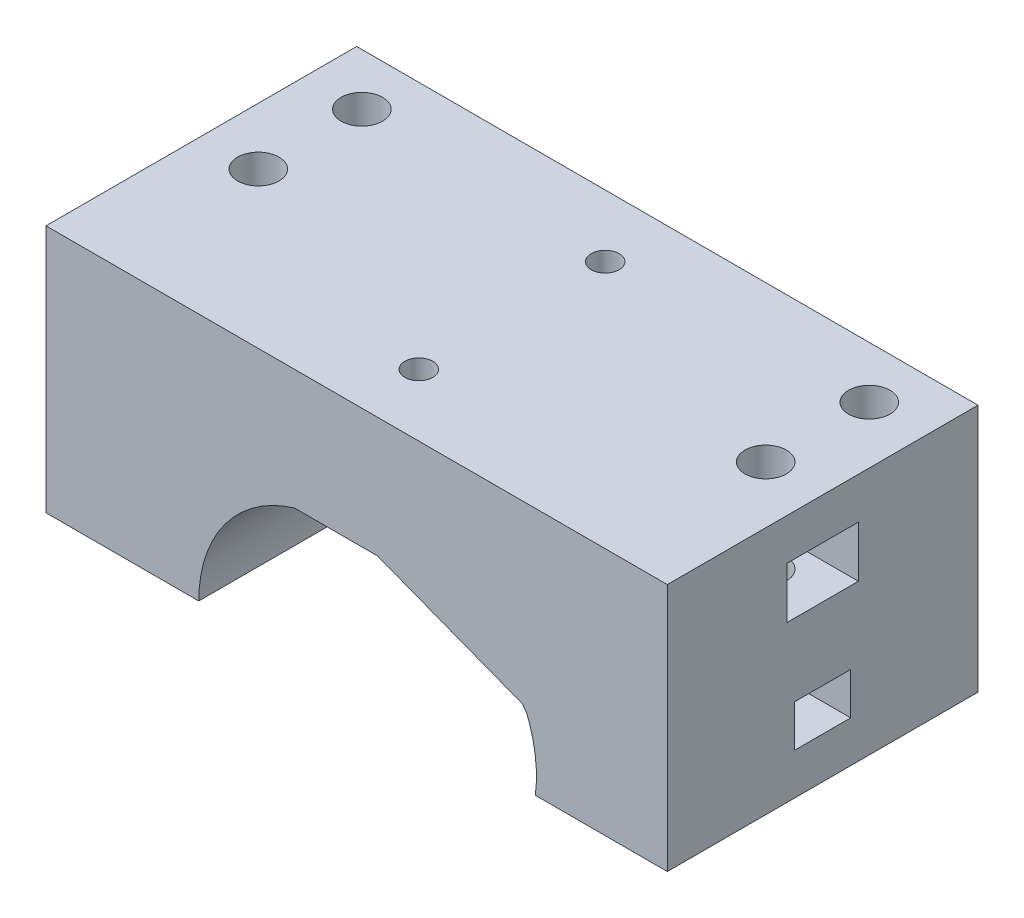
SolidWorks part; units mm, degrees
material "6061 合金"
ref_plane "前视基准面" through (0, 0, 0) normal (0, 0, 1) x (1, 0, 0)
ref_plane "上视基准面" through (0, 0, 0) normal (0, 1, 0) x (1, 0, 0)
ref_plane "右视基准面" through (0, 0, 0) normal (1, 0, 0) x (0, 0, -1)
sketch "草图1" plane through (0, 0, 0) normal (0, 0, 1) x (1, 0, 0)
  line L1 (-30, 17) -> (30, 17)
  line L2 (-30, 17) -> (-30, -17)
  line L3 (-30, -17) -> (30, -17)
  line L4 (30, 17) -> (30, -17)
  line L5 (-30, 17) -> (30, -17) construction
  line L6 (-30, -17) -> (30, 17) construction
  point P0 (0, 0)
  dimension "D1" = 34
  dimension "D2" = 60
extrude "凸台-拉伸1" add sketch "草图1" along normal blind 30
sketch "草图2" plane through (0, 0, 30) normal (0, 0, 1) x (1, 0, 0)
  line L0 (0, 0) -> (7.95, 0) construction
  line L1 (-11.5, 0) -> (-13.5, 0)
  line L2 (-13.5, 0) -> (-13.5, 15.766)
  line L4 (0, 0) -> (-35, 0)
  line L5 (-35, 0) -> (-35, 6.18)
  line L6 (-35, 6.18) -> (22.6518, 15.3111)
  line L7 (-13.5, 15.766) -> (-8.5, 15.766)
  line L8 (-8.5, 15.766) -> (-8.5, 10.3779)
  line L9 (0, 0) -> (11.5, 0)
  line L10 (11.5, 0) -> (11.5, 7.35)
  line L11 (0, 0) -> (0, -6.5) construction
  arc A0 (-8.5, 10.3779) -> (-11.5, 0) centre (7.95, 0) ccw
  arc A1 (-2.4955, 11.3282) -> (11.5, 7.35) centre (0, -6.5) cw
  dimension "D2" = 19.45
  dimension "D1" = 7.95
  dimension "D3" = 3
  dimension "D4" = 5
  dimension "D5" = 35
  dimension "D6" = 9
  dimension "D7" = 6.18
  dimension "D8" = 11.5
  dimension "D9" = 7.35
  dimension "D10" = 6.5
extrude "切除-拉伸1" [suppressed] cut sketch "草图2" against normal through all contours A1 L6 A0 L4 L9 L10
mirror "镜向1" [suppressed] about plane through (0, 0, 0) normal (0, 1, 0)
fillet "圆角1" [suppressed] radius 2
fillet "圆角2" [suppressed] radius 1
sketch "草图3" [suppressed] plane through (0, 0, 30) normal (0, 0, 1) x (1, 0, 0)
  line L0 (0, 0) -> (10.98, 0) construction
  line L1 (11.5, -6.8723) -> (11.5, 6.8723) construction
  line L2 (11.5, 8.0833) -> (11.5, -8.0833)
  arc A0 (11.5, 8.0833) -> (11.5, -8.0833) centre (10.98, 0) cw
  dimension "D2" = 8.1
  dimension "D1" = 10.98
extrude "切除-拉伸2" [suppressed] cut sketch "草图3" against normal through all
sketch "草图4" plane through (-30, 0, 0) normal (-1, 0, 0) x (0, 0, 1)
  line L0 (-9.8218, 0) -> (27.8243, 0) construction
  line L1 (0, 17) -> (30, 17)
  line L2 (0, 17) -> (0, 28)
  line L3 (0, 28) -> (30, 28)
  line L4 (30, 17) -> (30, 28)
  line L5 (30, 17) -> (30, -17) construction
  line L6 (15, 28) -> (15, -28) construction
  line L7 (0, -17) -> (30, -17)
  line L8 (0, -17) -> (0, -28)
  line L9 (0, -28) -> (30, -28)
  line L10 (30, -17) -> (30, -28)
  circle A0 centre (15, 24) radius 1.6
  circle A1 centre (15, -24) radius 1.6
  dimension "D2" = 3.2
  dimension "D3" = 48
  dimension "D1" = 56
extrude "凸台-拉伸2" [suppressed] add sketch "草图4" along normal blind 6 from surface
sketch "草图5" [suppressed] plane through (0, -17, 0) normal (0, -1, 0) x (1, 0, 0)
  line L1 (-20, 20) -> (20, 20)
  line L2 (-20, 20) -> (-20, 0)
  line L3 (-20, 0) -> (20, 0)
  line L4 (20, 20) -> (20, 0)
fillet "圆角3" [suppressed] radius 10
sketch "草图8" plane through (0, 0, 30) normal (0, 0, 1) x (1, 0, 0)
sketch "草图9" [suppressed] plane through (0, 0, 30) normal (0, 0, 1) x (1, 0, 0)
  line L1 (-37, 17) -> (-12, 17)
  line L2 (-37, 17) -> (-37, 29)
  line L3 (-37, 29) -> (-12, 29)
  line L4 (-12, 17) -> (-12, 29)
  line L5 (30, 0) -> (-45.0994, 0) construction
  line L7 (30, -28) -> (30, 28) construction
  line L8 (-12, -17) -> (-12, -29)
  line L9 (-37, -29) -> (-12, -29)
  line L10 (-37, -17) -> (-37, -29)
  line L11 (-37, -17) -> (-12, -17)
  line L12 (-31, 24.5) -> (-21, 24.5) construction
  line L13 (24, 17) -> (-30, 17) construction
  line L14 (24, 17) -> (24, 28) construction
  circle A0 centre (-31, 24.5) radius 2
  circle A1 centre (-21, 24.5) radius 2
  circle A2 centre (-21, -24.5) radius 2
  circle A3 centre (-31, -24.5) radius 2
  dimension "D3" = 49
  dimension "D4" = 4
  dimension "D5" = 4
  dimension "D6" = 10
  dimension "D7" = 36
  dimension "D8" = 45
  dimension "D1" = 12
  dimension "D2" = 25
extrude "凸台-拉伸5" [suppressed] add sketch "草图9" against normal blind 65
fillet "圆角4" [suppressed] radius 10
sketch "草图10" [suppressed] plane through (-37, 0, 0) normal (-1, 0, 0) x (0, 0, 1)
  line L0 (0, 0) -> (61.2796, 0) construction
  line L1 (30, -17) -> (30, -29) construction
  circle A0 centre (15, 24) radius 2.1
  circle A1 centre (15, -24) radius 2.1
  dimension "D1" = 4.2
  dimension "D2" = 48
  dimension "D3" = 15
extrude "切除-拉伸3" [suppressed] cut sketch "草图10" against normal blind 40
fillet "圆角5" [suppressed] radius 6
extrude "凸台-拉伸3" [suppressed] add sketch "草图5" along normal blind 60
sketch "草图6" [suppressed] plane through (0, 0, 20) normal (0, 0, 1) x (1, 0, 0)
  line L0 (-20, 17) -> (-20, -77) construction
  line L1 (20, -77) -> (-20, -77)
  line L2 (20, -77) -> (20, -27)
  line L3 (20, -27) -> (-20, -27)
  line L4 (-20, -77) -> (-20, -27)
  dimension "D1" = 50
extrude "凸台-拉伸4" [suppressed] add sketch "草图6" along normal blind 60
sketch "草图12" [suppressed] plane through (0, -29, 0) normal (0, -1, 0) x (1, 0, 0)
  line L0 (-37, -35) -> (-37, 30) construction
  line L1 (-34.4, -18.7) -> (-17.2, -18.7)
  line L2 (-34.4, -18.7) -> (-34.4, -23)
  line L3 (-34.4, -23) -> (-17.2, -23)
  line L4 (-17.2, -18.7) -> (-17.2, -23)
  line L5 (-37, -35) -> (-12, -35) construction
  dimension "D1" = 4.3
  dimension "D2" = 17.2
  dimension "D3" = 2.6
  dimension "D4" = 12
extrude "切除-拉伸4" [suppressed] cut sketch "草图12" against normal blind 8.8
mirror "镜向2" [suppressed] about plane through (0, 0, 0) normal (0, 1, 0)
sketch "草图13" [suppressed] plane through (0, 0, 30) normal (0, 0, 1) x (1, 0, 0)
  circle A0 centre (-21, 24.5) radius 2
  circle A1 centre (-31, 24.5) radius 2
  circle A2 centre (-31, -24.5) radius 2
  circle A3 centre (-21, -24.5) radius 2
extrude "凸台-拉伸6" [suppressed] add sketch "草图13" against normal blind 40
sketch "草图17" plane through (0, 0, 0) normal (0, 0, -1) x (-1, 0, 0)
  line L0 (-30, 17) -> (30, 17) construction
  line L1 (30, 17) -> (18, 17)
  line L2 (30, 17) -> (30, 40)
  line L3 (30, 40) -> (18, 40)
  line L4 (18, 17) -> (18, 40)
  line L5 (-18, 17) -> (-30, 17)
  line L6 (-18, 17) -> (-18, 40)
  line L7 (-18, 40) -> (-30, 40)
  line L8 (-30, 17) -> (-30, 40)
  line L9 (-30, -17) -> (-30, 17) construction
  dimension "D1" = 23
  dimension "D2" = 23
  dimension "D3" = 12
  dimension "D4" = 12
extrude "凸台-拉伸8" add sketch "草图17" against normal blind 80
sketch "草图18" plane through (0, 0, 80) normal (0, 0, 1) x (1, 0, 0)
  line L0 (0, 0) -> (0, 43.5188) construction
  line L1 (18, 40) -> (30, 40) construction
  circle A0 centre (24.5, 34) radius 2
  circle A1 centre (24.5, 24) radius 2
  circle A2 centre (-24.5, 24) radius 2
  circle A3 centre (-24.5, 34) radius 2
  dimension "D1" = 49
  dimension "D2" = 49
  dimension "D3" = 4
  dimension "D4" = 4
  dimension "D5" = 10
  dimension "D6" = 6
extrude "切除-拉伸7" cut sketch "草图18" against normal blind 10
sketch "草图19" plane through (0, 0, 30) normal (0, 0, 1) x (1, 0, 0)
  line L0 (2, 12.4) -> (-6, 12.4)
  line L1 (2, 12.4) -> (16.0037, 7.0245)
  line L2 (2, 0) -> (2, 12.4) construction
  line L3 (2, 0) -> (-30, 0) construction
  line L4 (-30, 17) -> (-30, -17) construction
  line L5 (2, -12.4) -> (-6, -12.4)
  line L6 (2, -12.4) -> (16.0037, -7.0245)
  line L7 (18, 17) -> (-18, 17) construction
  line L8 (6.25, 0) -> (0, 0) construction
  line L9 (-30, -17) -> (30, -17) construction
  line L10 (0, 0) -> (-3.1579, 0) construction
  line L11 (-2.4742, 0) -> (1.2749, 0) construction
  arc A3 (16.0037, 7.0245) -> (16.0037, -7.0245) centre (-3.1579, 0) cw
  arc A4 (-6, 12.4) -> (-6, -12.4) centre (-2.3127, 0) ccw
  point P10 (1.2749, 0)
  point P21 (17.2507, 0)
  point P36 (-15.2493, 0)
  dimension "D6" = 2
  dimension "D7" = 15
  dimension "D3" = 32.5
  dimension "D9" = 15
  dimension "D1" = 12.4
  dimension "D2" = 8
  dimension "D4" = 21
  dimension "D8" = 21
extrude "切除-拉伸8" cut sketch "草图19" against normal blind 66
sketch "草图20" plane through (30, 0, 0) normal (1, 0, 0) x (0, 0, -1)
  line L0 (-80, 40) -> (-80, 17) construction
  line L1 (-70, 37.4) -> (-65.5, 37.4)
  line L2 (-70, 37.4) -> (-70, 20.2)
  line L3 (-70, 20.2) -> (-65.5, 20.2)
  line L4 (-65.5, 37.4) -> (-65.5, 20.2)
  line L5 (-80, 40) -> (0, 40) construction
  dimension "D1" = 10
  dimension "D2" = 4.5
  dimension "D3" = 2.6
  dimension "D4" = 17.2
extrude "切除-拉伸9" cut sketch "草图20" against normal blind 8.8
sketch "草图14" plane through (0, -17, 0) normal (0, -1, 0) x (1, 0, 0)
  line L0 (0, 0) -> (0, 30) construction
  line L1 (-28, 0) -> (28, 0)
  line L2 (-28, 0) -> (-28, 30)
  line L3 (-28, 30) -> (28, 30)
  line L4 (28, 0) -> (28, 30)
  line L5 (-28, 0) -> (28, 30) construction
  line L6 (-28, 30) -> (28, 0) construction
  line L7 (0, 15) -> (24.5, 15) construction
  line L8 (-30, 30) -> (30, 30) construction
  line L9 (-30, 0) -> (30, 0) construction
  line L10 (30, 30) -> (18, 30) construction
  circle A0 centre (24.5, 15) radius 1.6
  circle A1 centre (-24.5, 15) radius 1.6
  point P0 (0, 15)
  dimension "D2" = 3.2
  dimension "D3" = 49
  dimension "D1" = 56
extrude "切除-拉伸6" cut sketch "草图14" against normal through all contours A0 | A1 region at (24.5, -17, 15) region at (-24.5, -17, 15)
mirror "镜向3" about plane through (0, 0, 0) normal (1, 0, 0) of "切除-拉伸9"
sketch "草图21" plane through (0, -17, 0) normal (0, -1, 0) x (1, 0, 0)
  line L1 (-30, 30) -> (30, 30)
  line L2 (-30, 30) -> (-30, 0)
  line L3 (-30, 0) -> (30, 0)
  line L4 (30, 30) -> (30, 0)
  circle A0 centre (24.5, 15) radius 1.6
  circle A1 centre (-24.5, 15) radius 1.6
extrude "凸台-拉伸9" add sketch "草图21" along normal blind 7
sketch "草图22" plane through (0, 17, 0) normal (0, 1, 0) x (1, 0, 0)
  line L1 (-18, 0) -> (18, 0)
  line L2 (-18, 0) -> (-18, -30)
  line L3 (-18, -30) -> (18, -30)
  line L4 (18, 0) -> (18, -30)
extrude "凸台-拉伸10" add sketch "草图22" along normal blind 7
sketch "草图25" plane through (-30, 0, 0) normal (-1, 0, 0) x (0, 0, 1)
  line L0 (0, 40) -> (0, -24) construction
  line L1 (0, 24) -> (30, 24)
  line L2 (0, 24) -> (0, -24)
  line L3 (0, -24) -> (30, -24)
  line L4 (30, 24) -> (30, -24)
  line L5 (0, 24) -> (30, -24) construction
  line L6 (0, -24) -> (30, 24) construction
  line L7 (8, 16) -> (8, -16) construction
  line L8 (15, 0) -> (15, -12.6905) construction
  circle A0 centre (8, -16) radius 1.5
  circle A1 centre (8, 16) radius 1.5
  circle A2 centre (22, -16) radius 1.5
  circle A3 centre (22, 16) radius 1.5
  point P0 (15, 0)
  point P11 (15, 0)
  dimension "D2" = 3
  dimension "D3" = 3
  dimension "D1" = 32
  dimension "D4" = 7
extrude "切除-拉伸12" [suppressed] cut sketch "草图25" against normal blind 108 contours A1 | A0 | A3 | A2
sketch "草图23" plane through (0, 0, 0) normal (1, 0, 0) x (0, 0, -1)
  line L1 (34.3948, -41.3985) -> (-105.7517, -41.3985)
  line L2 (34.3948, -41.3985) -> (34.3948, 61.9184)
  line L3 (34.3948, 61.9184) -> (-105.7517, 61.9184)
  line L4 (-105.7517, -41.3985) -> (-105.7517, 61.9184)
extrude "切除-拉伸10" [suppressed] cut sketch "草图23" against normal blind 108
sketch "草图24" plane through (0, 0, 0) normal (1, 0, 0) x (0, 0, -1)
  line L5 (-94.0825, 62.2673) -> (30.5955, 62.2673)
  line L6 (-94.0825, 62.2673) -> (-94.0825, -43.8021)
  line L7 (-94.0825, -43.8021) -> (30.5955, -43.8021)
  line L8 (30.5955, 62.2673) -> (30.5955, -43.8021)
extrude "切除-拉伸11" [suppressed] cut sketch "草图24" along normal blind 108
sketch "草图27" plane through (0, 17, 0) normal (0, -1, 0) x (1, 0, 0)
  line L1 (18, 30) -> (30, 30)
  line L2 (18, 30) -> (18, 80)
  line L3 (18, 80) -> (30, 80)
  line L4 (30, 30) -> (30, 80)
extrude "切除-拉伸13" cut sketch "草图27" against normal through all
ref_plane "基准面1" through (18, 40, 30) normal (1, 0, 0) x (0, 0, -1)
sketch "草图29" plane through (0, 0, 30) normal (0, 0, 1) x (1, 0, 0)
  line L1 (18, 24) -> (30, 24)
  line L2 (18, 24) -> (18, 40)
  line L3 (18, 40) -> (30, 40)
  line L4 (30, 24) -> (30, 40)
extrude "切除-拉伸14" cut sketch "草图29" against normal through all
sketch "草图30" [suppressed] plane through (0, 17, 0) normal (0, -1, 0) x (1, 0, 0)
  line L1 (-30, 80) -> (-18, 80)
  line L2 (-30, 80) -> (-30, 30)
  line L3 (-30, 30) -> (-18, 30)
  line L4 (-18, 80) -> (-18, 30)
extrude "切除-拉伸15" [suppressed] cut sketch "草图30" against normal through all
sketch "草图31" [suppressed] plane through (0, 0, 30) normal (0, 0, 1) x (1, 0, 0)
  line L1 (-18, 24) -> (-30, 24)
  line L2 (-18, 24) -> (-18, 40)
  line L3 (-18, 40) -> (-30, 40)
  line L4 (-30, 24) -> (-30, 40)
extrude "切除-拉伸16" [suppressed] cut sketch "草图31" against normal blind 87
sketch "草图32" [suppressed] plane through (0, 0, 30) normal (0, 0, 1) x (1, 0, 0)
  line L0 (-10, 24) -> (-13.4641, 22)
  line L2 (-30, 24) -> (0, 24) construction
  line L3 (-13.4641, 22) -> (0, 22)
  line L4 (0, 12.25) -> (0, 24) construction
  line L5 (-10, 24) -> (0, 24)
  line L6 (0, 24) -> (0, 22)
  dimension "D1" = 3
  dimension "D2" = 10
  dimension "D3" = 40
extrude "切除-拉伸17" [suppressed] cut sketch "草图32" against normal through all
sketch "草图33" [suppressed] plane through (0, 0, 30) normal (0, 0, 1) x (1, 0, 0)
  line L0 (13.5753, 21) -> (10, 24)
  line L1 (10, 24) -> (0, 24)
  line L2 (13.5753, 21) -> (0, 21)
  line L3 (0, 21) -> (0, 24)
  line L4 (0, 24) -> (30, 24) construction
  dimension "D1" = 40
  dimension "D2" = 10
  dimension "D3" = 3
extrude "切除-拉伸18" [suppressed] cut sketch "草图33" against normal through all
sketch "草图34" plane through (30, 0, 0) normal (1, 0, 0) x (0, 0, -1)
  line L0 (0, 0) -> (-30, 0) construction
  line L1 (-30, -24) -> (-30, 24) construction
  line L2 (0, -24) -> (0, 24) construction
  line L3 (-30, -11) -> (0, -11)
  line L4 (-30, -11) -> (-30, 11)
  line L5 (-30, 11) -> (0, 11)
  line L6 (0, -11) -> (0, 11)
  line L7 (-30, -11) -> (0, 11) construction
  line L8 (-30, 11) -> (0, -11) construction
  point P5 (-15, 0)
  dimension "D1" = 22
extrude "切除-拉伸19" [suppressed] cut sketch "草图34" against normal blind 8
sketch "草图35" [suppressed] plane through (-30, 0, 0) normal (-1, 0, 0) x (0, 0, 1)
  line L0 (0, 0) -> (30, 0) construction
  line L1 (30, 24) -> (30, -24) construction
  line L3 (0, -11) -> (30, -11)
  line L4 (0, -11) -> (0, 11)
  line L5 (0, 11) -> (30, 11)
  line L6 (30, -11) -> (30, 11)
  line L7 (0, -11) -> (30, 11) construction
  line L8 (0, 11) -> (30, -11) construction
  point P5 (15, 0)
  dimension "D1" = 22
extrude "切除-拉伸20" [suppressed] cut sketch "草图35" against normal blind 8
sketch "草图36" plane through (0, 0, 80) normal (0, 0, 1) x (1, 0, 0)
  line L1 (-30, 40) -> (-18, 40)
  line L2 (-30, 40) -> (-30, 17)
  line L3 (-30, 17) -> (-18, 17)
  line L4 (-18, 40) -> (-18, 17)
extrude "切除-拉伸21" cut sketch "草图36" against normal up to surface (50 mm away) up to face at (-6, 5.6667, 30)
sketch "草图37" plane through (0, 0, 30) normal (0, 0, 1) x (1, 0, 0)
  line L1 (-30, 40) -> (-18, 40)
  line L2 (-30, 40) -> (-30, 24)
  line L3 (-30, 24) -> (-18, 24)
  line L4 (-18, 40) -> (-18, 24)
extrude "切除-拉伸22" cut sketch "草图37" against normal through all
mirror "镜向4" [suppressed] about plane through (0, 0, 0) normal (1, 0, 0)
sketch "草图38" plane through (0, 0, 0) normal (0, 1, 0) x (1, 0, 0)
  line L1 (-30, 0) -> (30, 0)
  line L2 (-30, 0) -> (-30, -30)
  line L3 (-30, -30) -> (30, -30)
  line L4 (30, 0) -> (30, -30)
extrude "切除-拉伸23" cut sketch "草图38" against normal blind 34
sketch "草图40" plane through (0, 0, 30) normal (0, 0, 1) x (1, 0, 0)
  line L0 (0, 0) -> (0, 51.3105) construction
  line L1 (-10, 24) -> (-13.5753, 27)
  line L2 (-30, 24) -> (30, 24) construction
  line L3 (-13.5753, 27) -> (13.5753, 27)
  line L4 (10, 24) -> (13.5753, 27)
  line L5 (-10, 24) -> (10, 24)
  line L6 (-30, 24) -> (36.4336, 24) construction
  line L7 (-10, 24) -> (-13.5753, 21)
  line L8 (-13.5753, 21) -> (13.5753, 21)
  line L9 (10, 24) -> (13.5753, 21)
  point P10 (0, 27)
  line M8 (30, 24) -> (-30, 24)
  dimension "D1" = 3
  dimension "D2" = 40
  dimension "D3" = 10
extrude "切除-拉伸24" [suppressed] cut sketch "草图40" against normal up to surface (30 mm away) contours L9 L7 L8 M8
sketch "草图41" plane through (30, 0, 0) normal (1, 0, 0) x (0, 0, -1)
  line L0 (-15, 0) -> (-15, 24) construction
  line L1 (-30, 0) -> (0, 0) construction
  line L2 (0, 24) -> (-30, 24) construction
  line L6 (-18.45, 20) -> (-11.55, 20)
  line L7 (-18.45, 20) -> (-18.45, 15.05)
  line L8 (-18.45, 15.05) -> (-11.55, 15.05)
  line L9 (-11.55, 20) -> (-11.55, 15.05)
  line L10 (-18.45, 20) -> (-11.55, 15.05) construction
  line L11 (-18.45, 15.05) -> (-11.55, 20) construction
  line L12 (-17.705, 8.05) -> (-12.295, 8.05)
  line L13 (-17.705, 8.05) -> (-17.705, 4)
  line L14 (-17.705, 4) -> (-12.295, 4)
  line L15 (-12.295, 8.05) -> (-12.295, 4)
  line L16 (-17.705, 8.05) -> (-12.295, 4) construction
  line L17 (-17.705, 4) -> (-12.295, 8.05) construction
  point P6 (-15, 6.025)
  point P10 (-15, 17.525)
  dimension "D1" = 4.05
  dimension "D2" = 4.95
  dimension "D3" = 6.9
  dimension "D4" = 5.41
  dimension "D5" = 4
  dimension "D6" = 4
extrude "切除-拉伸25" cut sketch "草图41" against normal blind 5.5
mirror "镜向5" about plane through (0, 0, 0) normal (1, 0, 0) of "切除-拉伸25"
sketch "草图42" plane through (0, 0, 30) normal (0, 0, 1) x (1, 0, 0)
  line L0 (16.0037, 7.0245) -> (14.503, 1.3945)
  line L1 (14.503, 1.3945) -> (17.2507, 0)
  spline S0 degree 1 poles (16.0037, 7.0245) (16.4413, 6.4186) knots 0 0 1 1
  spline S1 degree 2 poles (16.4413, 6.4186) (17.6799, 3.2616) (17.2507, 0) knots 0 0 0 1 1 1
extrude "切除-拉伸26" cut sketch "草图42" against normal through all
sketch "草图43" plane through (0, 24, 0) normal (0, 1, 0) x (1, 0, 0)
  line L0 (30, 0) -> (-30, 0) construction
  line L1 (0, 0) -> (0, -30) construction
  line L2 (-30, -30) -> (30, -30) construction
  line L3 (30, -15) -> (-30, -15) construction
  line L4 (30, 0) -> (30, -30) construction
  line L5 (-30, 0) -> (-30, -30) construction
  circle A0 centre (0, -6) radius 1.35
  circle A1 centre (0, -24) radius 1.35
  dimension "D1" = 2.7
  dimension "D2" = 6
extrude "切除-拉伸27" cut sketch "草图43" against normal through all
sketch "草图44" [suppressed] plane through (0, 21, 0) normal (0, 1, 0) x (1, 0, 0)
  line L0 (0, 0) -> (0, -30) construction
  line L1 (-13.5753, -30) -> (13.5753, -30) construction
  line L2 (13.5753, 0) -> (-13.5753, 0) construction
  line L3 (30, -15) -> (-30, -15) construction
  line L4 (30, 0) -> (30, -30) construction
  line L5 (-30, 0) -> (-30, -30) construction
  circle A0 centre (0, -6) radius 1.4
  circle A1 centre (0, -24) radius 1.4
  dimension "D1" = 2.8
  dimension "D2" = 6
extrude "切除-拉伸28" [suppressed] cut sketch "草图44" against normal blind 10
sketch "草图47" plane through (0, 24, 0) normal (0, 1, 0) x (1, 0, 0)
  circle A0 centre (-24.5, -15) radius 1.9
  circle A1 centre (24.5, -15) radius 1.9
  dimension "D1" = 3.8
  dimension "D2" = 3.8
extrude "切除-拉伸29" cut sketch "草图47" against normal blind 7
sketch "草图48" plane through (0, 24, 0) normal (0, 1, 0) x (1, 0, 0)
  line L0 (-30, 0) -> (-30, -30) construction
  line L1 (0, 0) -> (0, -30) construction
  line L2 (-30, -30) -> (30, -30) construction
  circle A0 centre (-24.5, -5) radius 2
  circle A1 centre (-24.5, -15) radius 1.6 construction
  circle A2 centre (24.5, -5) radius 2
  dimension "D1" = 4
  dimension "D3" = 10
  dimension "D2" = 5.5
extrude "切除-拉伸30" cut sketch "草图48" against normal blind 10
sketch "草图49" plane through (0, 24, 0) normal (0, 1, 0) x (1, 0, 0)
  line L0 (-28.4837, -5) -> (-28.4837, 0)
  line L1 (-20.5163, -5) -> (-22.5081, -1.55)
  line L2 (-22.5081, -1.55) -> (-26.4919, -1.55)
  line L3 (-26.4919, -1.55) -> (-28.4837, -5)
  line L4 (-28.4837, -5) -> (-26.4919, -8.45)
  line L5 (-26.4919, -8.45) -> (-22.5081, -8.45)
  line L6 (-22.5081, -8.45) -> (-20.5163, -5)
  line L7 (30, 0) -> (-30, 0) construction
  line L8 (-28.4837, 0) -> (-20.5163, 0)
  line L9 (-20.5163, 0) -> (-20.5163, -5)
  circle A0 centre (-24.5, -5) radius 3.45 construction
  circle M7 centre (-24.5, -5) radius 2
  line M13 (30, 0) -> (-30, 0)
  dimension "D1" = 6.9
extrude "切除-拉伸31" cut sketch "草图49" against normal blind 4.9 from offset 4 contours L5 L6 L1 L2 L3 L4 M7 | L9 L0 L3 L2 L1 M13 region at (-24.5, 24, 1.4632) region at (-27.3965, 24, 3.3277) offset against normal yes
mirror "镜向6" about plane through (0, 0, 0) normal (1, 0, 0) of "切除-拉伸31"
sketch "草图51" plane through (0, 8.05, 0) normal (0, -1, 0) x (1, 0, 0)
  line L0 (24.5, 17.705) -> (30, 17.705) construction
  line L1 (26.0617, 17.705) -> (22.9383, 17.705)
  line L2 (22.9383, 17.705) -> (21.3765, 15)
  line L3 (21.3765, 15) -> (22.9383, 12.295)
  line L4 (22.9383, 12.295) -> (26.0617, 12.295)
  line L5 (26.0617, 12.295) -> (27.6235, 15)
  line L6 (27.6235, 15) -> (26.0617, 17.705)
  circle A0 centre (24.5, 15) radius 2.705 construction
extrude "切除-拉伸32" cut sketch "草图51" along normal up to surface (4.05 mm away) up to face at (26.6, 4, 15)
sketch "草图52" plane through (0, 15.05, 0) normal (0, 1, 0) x (1, 0, 0)
  line L0 (24.5, -11.55) -> (30, -11.55) construction
  line L1 (26.4919, -11.55) -> (22.5081, -11.55)
  line L2 (22.5081, -11.55) -> (20.5163, -15)
  line L3 (20.5163, -15) -> (22.5081, -18.45)
  line L4 (22.5081, -18.45) -> (26.4919, -18.45)
  line L5 (26.4919, -18.45) -> (28.4837, -15)
  line L6 (28.4837, -15) -> (26.4919, -11.55)
  circle A0 centre (24.5, -15) radius 3.45 construction
extrude "切除-拉伸33" cut sketch "草图52" along normal up to surface (4.95 mm away) up to face at (26.65, 20, 15)
mirror "镜向7" about plane through (0, 0, 0) normal (1, 0, 0) of "切除-拉伸33", "切除-拉伸32"
sketch "草图53" plane through (0, 24, 0) normal (0, 1, 0) x (1, 0, 0)
  circle A0 centre (-24.5, -15) radius 2
  circle A1 centre (24.5, -15) radius 2
  dimension "D1" = 4
  dimension "D2" = 4
extrude "切除-拉伸34" cut sketch "草图53" against normal up to surface (15.95 mm away)
